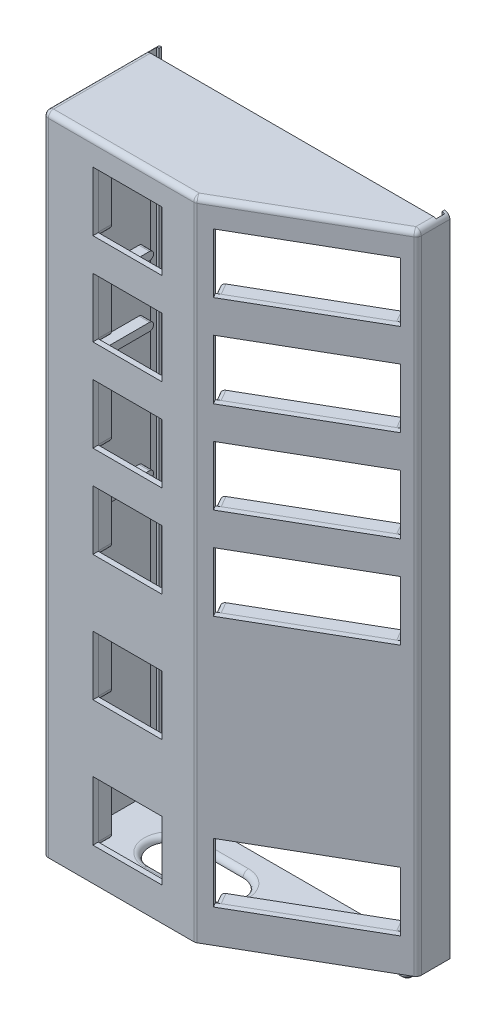
SolidWorks part; units mm, degrees
ref_plane "Front Plane" through (0, 0, 0) normal (0, 0, 1) x (1, 0, 0)
ref_plane "Top Plane" through (0, 0, 0) normal (0, 1, 0) x (1, 0, 0)
ref_plane "Right Plane" through (0, 0, 0) normal (1, 0, 0) x (0, 0, -1)
sketch "Sketch2" plane through (0, 0, 0) normal (0, 1, 0) x (1, 0, 0)
  line L0 (-55, -21.2241) -> (-55, 21.2241)
  line L1 (-55, 21.2241) -> (55, 21.2241)
  line L2 (55, 21.2241) -> (55, 9.3594)
  line L3 (55, 9.3594) -> (2.0277, -21.2241)
  line L4 (2.0277, -21.2241) -> (-55, -21.2241)
  line L5 (0, 21.2241) -> (0, -21.2241) construction
  point P11 (0, 21.2241)
  point P12 (0, 0)
  dimension "D1" = 42.4483
  dimension "D2" = 110
  dimension "D3" = 57.0277
  dimension "D4" = 30
extrude "Main Body" add sketch "Sketch2" along normal blind 241.93
shell "Shell1" thickness 2 removed face at (0, 120.965, -21.2241)
sketch "Sketch3" plane through (0, 0, 21.2241) normal (0, 0, 1) x (1, 0, 0)
  line L1 (-36.2923, 34.72) -> (-10.4223, 34.72)
  line L2 (-36.2923, 34.72) -> (-36.2923, 12.45)
  line L3 (-36.2923, 12.45) -> (-10.4223, 12.45)
  line L4 (-10.4223, 34.72) -> (-10.4223, 12.45)
  line L5 (-36.2923, 81.89) -> (-10.4223, 81.89)
  line L6 (-36.2923, 81.89) -> (-36.2923, 59.62)
  line L7 (-36.2923, 59.62) -> (-10.4223, 59.62)
  line L8 (-10.4223, 81.89) -> (-10.4223, 59.62)
  line L9 (-36.2923, 129.06) -> (-10.4223, 129.06)
  line L10 (-36.2923, 129.06) -> (-36.2923, 106.79)
  line L11 (-36.2923, 106.79) -> (-10.4223, 106.79)
  line L12 (-10.4223, 129.06) -> (-10.4223, 106.79)
  line L13 (-36.2923, 163.53) -> (-10.4223, 163.53)
  line L14 (-36.2923, 163.53) -> (-36.2923, 141.26)
  line L15 (-36.2923, 141.26) -> (-10.4223, 141.26)
  line L16 (-10.4223, 163.53) -> (-10.4223, 141.26)
  line L17 (-36.2923, 198) -> (-10.4223, 198)
  line L18 (-36.2923, 198) -> (-36.2923, 175.73)
  line L19 (-36.2923, 175.73) -> (-10.4223, 175.73)
  line L20 (-10.4223, 198) -> (-10.4223, 175.73)
  line L21 (-36.2923, 232.47) -> (-10.4223, 232.47)
  line L22 (-36.2923, 232.47) -> (-36.2923, 210.2)
  line L23 (-36.2923, 210.2) -> (-10.4223, 210.2)
  line L24 (-10.4223, 232.47) -> (-10.4223, 210.2)
  line L26 (-55, 0) -> (2.0277, 0) construction
  line L27 (-55, 241.93) -> (-55, 0) construction
  point P24 (-36.2923, 23.585)
  point P29 (-36.2923, 70.755)
  point P30 (-36.2923, 117.925)
  point P31 (-36.2923, 152.395)
  point P32 (-36.2923, 186.865)
  point P33 (-36.2923, 221.335)
  point P34 (-23.3573, 12.45)
  dimension "D1" = 22.27
  dimension "D2" = 25.87
  dimension "D3" = 23.585
  dimension "D4" = 47.17
  dimension "D5" = 47.17
  dimension "D6" = 34.47
  dimension "D7" = 34.47
  dimension "D8" = 34.47
  dimension "D9" = 31.6427
extrude "Single Cutouts" cut sketch "Sketch3" against normal through all both and the other way through all
sketch "Sketch4" plane through (9.6973, 0, 16.7961) normal (0.5, 0, 0.866) x (0.866, 0, -0.5)
  line L1 (-3.856, 232.47) -> (47.394, 232.47)
  line L2 (-3.856, 232.47) -> (-3.856, 210.2)
  line L3 (-3.856, 210.2) -> (47.394, 210.2)
  line L4 (47.394, 232.47) -> (47.394, 210.2)
  line L5 (-3.856, 198) -> (47.394, 198)
  line L6 (-3.856, 198) -> (-3.856, 175.73)
  line L7 (-3.856, 175.73) -> (47.394, 175.73)
  line L8 (47.394, 198) -> (47.394, 175.73)
  line L9 (-3.856, 163.53) -> (47.394, 163.53)
  line L10 (-3.856, 163.53) -> (-3.856, 141.26)
  line L11 (-3.856, 141.26) -> (47.394, 141.26)
  line L12 (47.394, 163.53) -> (47.394, 141.26)
  line L13 (-3.856, 129.06) -> (47.394, 129.06)
  line L14 (-3.856, 129.06) -> (-3.856, 106.79)
  line L15 (-3.856, 106.79) -> (47.394, 106.79)
  line L16 (47.394, 129.06) -> (47.394, 106.79)
  line L17 (-3.856, 34.72) -> (47.394, 34.72)
  line L18 (-3.856, 34.72) -> (-3.856, 12.45)
  line L19 (-3.856, 12.45) -> (47.394, 12.45)
  line L20 (47.394, 34.72) -> (47.394, 12.45)
  line L21 (-42.0421, 34.72) -> (-19.638, 34.72) construction
  line L22 (-42.0421, 129.06) -> (-19.638, 129.06) construction
  line L23 (-42.0421, 163.53) -> (-19.638, 163.53) construction
  line L24 (-42.0421, 198) -> (-19.638, 198) construction
  line L25 (-42.0421, 232.47) -> (-19.638, 232.47) construction
  line L26 (-19.638, 232.47) -> (-19.638, 210.2) construction
  line L27 (-8.856, 241.93) -> (-8.856, 0) construction
  dimension "D1" = 51.25
  dimension "D2" = 5
extrude "Double Cutouts" cut sketch "Sketch4" against normal through all both and the other way through all
sketch "Sketch5" plane through (0, 0, 0) normal (0, -1, 0) x (1, 0, 0)
  line L0 (-55, -21.2241) -> (-55, 21.2241) construction
  line L1 (-55, 21.2241) -> (2.0277, 21.2241) construction
  line L2 (55, -21.2241) -> (-55, -21.2241) construction
  line L3 (55, -9.3594) -> (55, -21.2241) construction
  circle A0 centre (47, -13.2241) radius 2.75
  circle A1 centre (-47, 13.2241) radius 2.75
  circle A2 centre (-47, -13.2241) radius 2.75
  circle A3 centre (-2, 13.2241) radius 2.75
  dimension "D3" = 8
  dimension "D4" = 5.5
  dimension "D5" = 45
  dimension "D6" = 8
  dimension "D1" = 8
  dimension "D2" = 8
extrude "Mating Studs" add sketch "Sketch5" along normal blind 5
chamfer "Mating Stud Chamfer" distance 1 angle 45 4 edges at (47, -5, -15.9741) (-47, -5, -15.9741) (-47, -5, 10.4741) (-2, -5, 10.4741)
sketch "Sketch6" plane through (0, 0, 0) normal (0, -1, 0) x (1, 0, 0)
  line L0 (-30, -1.2241) -> (-10, -1.2241) construction
  line L1 (-30, 6.2759) -> (-10, 6.2759)
  line L2 (-30, -8.7241) -> (-10, -8.7241)
  line L3 (55, -21.2241) -> (-55, -21.2241) construction
  line L4 (-55, -21.2241) -> (-55, 21.2241) construction
  arc A0 (-30, 6.2759) -> (-30, -8.7241) centre (-30, -1.2241) ccw
  arc A1 (-10, -8.7241) -> (-10, 6.2759) centre (-10, -1.2241) ccw
  point P2 (-20, -1.2241)
  dimension "D4" = 25
  dimension "D1" = 15
  dimension "D2" = 20
  dimension "D3" = 20
extrude "Pass Thru" cut sketch "Sketch6" against normal up to next
sketch "Sketch7" plane through (0, 0, 19.2241) normal (0, 0, -1) x (-1, 0, 0)
  line L0 (8.4073, 12.585) -> (8.4073, 34.585) construction
  line L1 (6.4073, 12.585) -> (6.4073, 34.585)
  line L2 (10.4073, 12.585) -> (10.4073, 34.585)
  line L3 (8.4073, 59.755) -> (8.4073, 81.755) construction
  line L4 (6.4073, 59.755) -> (6.4073, 81.755)
  line L5 (10.4073, 59.755) -> (10.4073, 81.755)
  line L6 (8.4073, 106.925) -> (8.4073, 128.925) construction
  line L7 (6.4073, 106.925) -> (6.4073, 128.925)
  line L8 (10.4073, 106.925) -> (10.4073, 128.925)
  line L9 (8.4073, 141.395) -> (8.4073, 163.395) construction
  line L10 (6.4073, 141.395) -> (6.4073, 163.395)
  line L11 (10.4073, 141.395) -> (10.4073, 163.395)
  line L12 (8.4073, 232.335) -> (8.4073, 210.335) construction
  line L13 (10.4073, 232.335) -> (10.4073, 210.335)
  line L14 (6.4073, 232.335) -> (6.4073, 210.335)
  line L15 (8.4073, 197.865) -> (8.4073, 175.865) construction
  line L16 (10.4073, 197.865) -> (10.4073, 175.865)
  line L17 (6.4073, 197.865) -> (6.4073, 175.865)
  line L18 (23.3573, 12.45) -> (23.3573, 81.89) construction
  line L19 (10.4223, 12.45) -> (36.2923, 12.45) construction
  line L20 (36.2923, 81.89) -> (10.4223, 81.89) construction
  line L21 (38.3073, 12.585) -> (38.3073, 34.585) construction
  line L22 (40.3073, 12.585) -> (40.3073, 34.585)
  line L23 (36.3073, 12.585) -> (36.3073, 34.585)
  line L24 (38.3073, 59.755) -> (38.3073, 81.755) construction
  line L25 (40.3073, 59.755) -> (40.3073, 81.755)
  line L26 (36.3073, 59.755) -> (36.3073, 81.755)
  line L27 (38.3073, 106.925) -> (38.3073, 128.925) construction
  line L28 (40.3073, 106.925) -> (40.3073, 128.925)
  line L29 (36.3073, 106.925) -> (36.3073, 128.925)
  line L30 (38.3073, 141.395) -> (38.3073, 163.395) construction
  line L31 (40.3073, 141.395) -> (40.3073, 163.395)
  line L32 (36.3073, 141.395) -> (36.3073, 163.395)
  line L33 (38.3073, 232.335) -> (38.3073, 210.335) construction
  line L34 (36.3073, 232.335) -> (36.3073, 210.335)
  line L35 (40.3073, 232.335) -> (40.3073, 210.335)
  line L36 (38.3073, 197.865) -> (38.3073, 175.865) construction
  line L37 (36.3073, 197.865) -> (36.3073, 175.865)
  line L38 (40.3073, 197.865) -> (40.3073, 175.865)
  line L39 (10.4223, 34.72) -> (10.4223, 12.45) construction
  line L40 (-5.3579, 23.585) -> (8.4073, 23.585) construction
  line L41 (-5.3579, 12.45) -> (-5.3579, 34.72) construction
  line L42 (-5.3579, 221.335) -> (8.4073, 221.335) construction
  line L43 (-5.3579, 210.2) -> (-5.3579, 232.47) construction
  line L44 (8.4073, 186.865) -> (-5.3579, 186.865) construction
  line L45 (-5.3579, 175.73) -> (-5.3579, 198) construction
  line L46 (-5.3579, 152.395) -> (8.4073, 152.395) construction
  line L47 (-5.3579, 141.26) -> (-5.3579, 163.53) construction
  line L48 (-5.3579, 117.925) -> (8.4073, 117.925) construction
  line L49 (-5.3579, 106.79) -> (-5.3579, 129.06) construction
  line L50 (10.4223, 70.755) -> (8.4073, 70.755) construction
  line L51 (10.4223, 81.89) -> (10.4223, 59.62) construction
  arc A0 (6.4073, 12.585) -> (10.4073, 12.585) centre (8.4073, 12.585) ccw
  arc A1 (10.4073, 34.585) -> (6.4073, 34.585) centre (8.4073, 34.585) ccw
  arc A2 (6.4073, 59.755) -> (10.4073, 59.755) centre (8.4073, 59.755) ccw
  arc A3 (10.4073, 81.755) -> (6.4073, 81.755) centre (8.4073, 81.755) ccw
  arc A4 (6.4073, 106.925) -> (10.4073, 106.925) centre (8.4073, 106.925) ccw
  arc A5 (10.4073, 128.925) -> (6.4073, 128.925) centre (8.4073, 128.925) ccw
  arc A6 (6.4073, 141.395) -> (10.4073, 141.395) centre (8.4073, 141.395) ccw
  arc A7 (10.4073, 163.395) -> (6.4073, 163.395) centre (8.4073, 163.395) ccw
  arc A8 (10.4073, 232.335) -> (6.4073, 232.335) centre (8.4073, 232.335) ccw
  arc A9 (6.4073, 210.335) -> (10.4073, 210.335) centre (8.4073, 210.335) ccw
  arc A10 (10.4073, 197.865) -> (6.4073, 197.865) centre (8.4073, 197.865) ccw
  arc A11 (6.4073, 175.865) -> (10.4073, 175.865) centre (8.4073, 175.865) ccw
  arc A12 (40.3073, 12.585) -> (36.3073, 12.585) centre (38.3073, 12.585) cw
  arc A13 (36.3073, 34.585) -> (40.3073, 34.585) centre (38.3073, 34.585) cw
  arc A14 (40.3073, 59.755) -> (36.3073, 59.755) centre (38.3073, 59.755) cw
  arc A15 (36.3073, 81.755) -> (40.3073, 81.755) centre (38.3073, 81.755) cw
  arc A16 (40.3073, 106.925) -> (36.3073, 106.925) centre (38.3073, 106.925) cw
  arc A17 (36.3073, 128.925) -> (40.3073, 128.925) centre (38.3073, 128.925) cw
  arc A18 (40.3073, 141.395) -> (36.3073, 141.395) centre (38.3073, 141.395) cw
  arc A19 (36.3073, 163.395) -> (40.3073, 163.395) centre (38.3073, 163.395) cw
  arc A20 (36.3073, 232.335) -> (40.3073, 232.335) centre (38.3073, 232.335) cw
  arc A21 (40.3073, 210.335) -> (36.3073, 210.335) centre (38.3073, 210.335) cw
  arc A22 (36.3073, 197.865) -> (40.3073, 197.865) centre (38.3073, 197.865) cw
  arc A23 (40.3073, 175.865) -> (36.3073, 175.865) centre (38.3073, 175.865) cw
  point P4 (8.4073, 23.585)
  point P9 (8.4073, 70.755)
  point P21 (8.4073, 117.925)
  point P28 (8.4073, 152.395)
  point P37 (8.4073, 221.335)
  point P46 (8.4073, 186.865)
  point P64 (38.3073, 23.585)
  point P71 (38.3073, 70.755)
  point P78 (38.3073, 117.925)
  point P85 (38.3073, 152.395)
  point P92 (38.3073, 221.335)
  point P99 (38.3073, 186.865)
  dimension "D1" = 0.015
  dimension "D2" = 4
  dimension "D3" = 22
extrude "PCB Mounts  - Single" add sketch "Sketch7" along normal blind 5
sketch "Sketch9" plane through (8.6973, 0, 15.0641) normal (-0.5, 0, -0.866) x (-0.866, 0, 0.5)
  line L0 (-45.844, 234.07) -> (2.306, 234.07) construction
  line L1 (-45.844, 235.57) -> (2.306, 235.57)
  line L2 (-45.844, 232.57) -> (2.306, 232.57)
  line L3 (-45.844, 208.6) -> (2.306, 208.6) construction
  line L4 (-45.844, 210.1) -> (2.306, 210.1)
  line L5 (-45.844, 207.1) -> (2.306, 207.1)
  line L6 (-45.844, 199.6) -> (2.306, 199.6) construction
  line L9 (-45.844, 201.1) -> (2.306, 201.1)
  line L10 (-45.844, 198.1) -> (2.306, 198.1)
  line L11 (-45.844, 174.13) -> (2.306, 174.13) construction
  line L12 (-45.844, 175.63) -> (2.306, 175.63)
  line L13 (-45.844, 172.63) -> (2.306, 172.63)
  line L14 (-45.844, 165.13) -> (2.306, 165.13) construction
  line L15 (-45.844, 166.63) -> (2.306, 166.63)
  line L16 (-45.844, 163.63) -> (2.306, 163.63)
  line L17 (-45.844, 139.66) -> (2.306, 139.66) construction
  line L18 (-45.844, 141.16) -> (2.306, 141.16)
  line L19 (-45.844, 138.16) -> (2.306, 138.16)
  line L20 (-45.844, 130.66) -> (2.306, 130.66) construction
  line L21 (-45.844, 132.16) -> (2.306, 132.16)
  line L22 (-45.844, 129.16) -> (2.306, 129.16)
  line L23 (-45.844, 105.19) -> (2.306, 105.19) construction
  line L24 (-45.844, 106.69) -> (2.306, 106.69)
  line L25 (-45.844, 103.69) -> (2.306, 103.69)
  line L26 (-45.844, 36.32) -> (2.306, 36.32) construction
  line L27 (-45.844, 37.82) -> (2.306, 37.82)
  line L28 (-45.844, 34.82) -> (2.306, 34.82)
  line L29 (-45.844, 10.85) -> (2.306, 10.85) construction
  line L30 (-45.844, 12.35) -> (2.306, 12.35)
  line L31 (-45.844, 9.35) -> (2.306, 9.35)
  line L32 (3.856, 34.72) -> (-47.394, 34.72) construction
  line L33 (-21.769, 10.85) -> (-21.769, 12.45) construction
  line L34 (-47.394, 12.45) -> (3.856, 12.45) construction
  line L35 (-21.769, 12.45) -> (-21.769, 242.0592) construction
  line L36 (-47.394, 106.79) -> (3.856, 106.79) construction
  line L37 (3.856, 129.06) -> (-47.394, 129.06) construction
  line L38 (-47.394, 141.26) -> (3.856, 141.26) construction
  line L39 (3.856, 163.53) -> (-47.394, 163.53) construction
  line L40 (-47.394, 175.73) -> (3.856, 175.73) construction
  line L41 (3.856, 198) -> (-47.394, 198) construction
  line L42 (-47.394, 210.2) -> (3.856, 210.2) construction
  line L43 (3.856, 232.47) -> (-47.394, 232.47) construction
  arc A0 (-45.844, 235.57) -> (-45.844, 232.57) centre (-45.844, 234.07) ccw
  arc A1 (2.306, 232.57) -> (2.306, 235.57) centre (2.306, 234.07) ccw
  arc A2 (-45.844, 210.1) -> (-45.844, 207.1) centre (-45.844, 208.6) ccw
  arc A3 (2.306, 207.1) -> (2.306, 210.1) centre (2.306, 208.6) ccw
  arc A6 (-45.844, 201.1) -> (-45.844, 198.1) centre (-45.844, 199.6) ccw
  arc A7 (2.306, 198.1) -> (2.306, 201.1) centre (2.306, 199.6) ccw
  arc A8 (-45.844, 175.63) -> (-45.844, 172.63) centre (-45.844, 174.13) ccw
  arc A9 (2.306, 172.63) -> (2.306, 175.63) centre (2.306, 174.13) ccw
  arc A10 (-45.844, 166.63) -> (-45.844, 163.63) centre (-45.844, 165.13) ccw
  arc A11 (2.306, 163.63) -> (2.306, 166.63) centre (2.306, 165.13) ccw
  arc A12 (-45.844, 141.16) -> (-45.844, 138.16) centre (-45.844, 139.66) ccw
  arc A13 (2.306, 138.16) -> (2.306, 141.16) centre (2.306, 139.66) ccw
  arc A14 (-45.844, 132.16) -> (-45.844, 129.16) centre (-45.844, 130.66) ccw
  arc A15 (2.306, 129.16) -> (2.306, 132.16) centre (2.306, 130.66) ccw
  arc A16 (-45.844, 106.69) -> (-45.844, 103.69) centre (-45.844, 105.19) ccw
  arc A17 (2.306, 103.69) -> (2.306, 106.69) centre (2.306, 105.19) ccw
  arc A18 (-45.844, 37.82) -> (-45.844, 34.82) centre (-45.844, 36.32) ccw
  arc A19 (2.306, 34.82) -> (2.306, 37.82) centre (2.306, 36.32) ccw
  arc A20 (-45.844, 12.35) -> (-45.844, 9.35) centre (-45.844, 10.85) ccw
  arc A21 (2.306, 9.35) -> (2.306, 12.35) centre (2.306, 10.85) ccw
  point P4 (-21.769, 234.07)
  point P9 (-21.769, 208.6)
  point P20 (-21.769, 199.6)
  point P21 (0, 0)
  point P26 (-21.769, 174.13)
  point P37 (-21.769, 165.13)
  point P46 (-21.769, 139.66)
  point P55 (-21.769, 130.66)
  point P64 (-21.769, 105.19)
  point P73 (-21.769, 36.32)
  point P82 (-21.769, 10.85)
  point P94 (0, 0)
  point P95 (0, 0)
  point P96 (0, 0)
  point P97 (0, 0)
  point P98 (0, 0)
  point P99 (0, 0)
  point P100 (0, 0)
  point P101 (0, 0)
  point P102 (0, 0)
  dimension "D1" = 3
  dimension "D2" = 48.15
  dimension "D3" = 0.1
  dimension "D4" = 0.1
  dimension "D5" = 0.1
  dimension "D6" = 0.1
  dimension "D7" = 0.1
  dimension "D8" = 0.1
  dimension "D9" = 0.1
  dimension "D10" = 0.1
  dimension "D11" = 0.1
  dimension "D12" = 0.1
extrude "PCB Mounts - Double" add sketch "Sketch9" along normal blind 5
sketch "Sketch11" plane through (-53, 0, 0) normal (1, 0, 0) x (0, 0, -1)
  line L0 (-12.2759, 228.43) -> (12.7241, 228.43) construction
  line L1 (-12.2759, 229.93) -> (12.7241, 229.93)
  line L2 (-12.2759, 226.93) -> (12.7241, 226.93)
  line L3 (-12.2759, 180.28) -> (12.7241, 180.28) construction
  line L4 (-12.2759, 181.78) -> (12.7241, 181.78)
  line L5 (-12.2759, 178.78) -> (12.7241, 178.78)
  line L6 (-12.2759, 157.28) -> (12.7241, 157.28) construction
  line L7 (-12.2759, 158.78) -> (12.7241, 158.78)
  line L8 (-12.2759, 155.78) -> (12.7241, 155.78)
  line L9 (-12.2759, 109.13) -> (12.7241, 109.13) construction
  line L10 (-12.2759, 110.63) -> (12.7241, 110.63)
  line L11 (-12.2759, 107.63) -> (12.7241, 107.63)
  line L12 (-12.2759, 71.13) -> (12.7241, 71.13) construction
  line L13 (-12.2759, 72.63) -> (12.7241, 72.63)
  line L14 (-12.2759, 69.63) -> (12.7241, 69.63)
  line L15 (-12.2759, 22.98) -> (12.7241, 22.98) construction
  line L16 (-12.2759, 24.48) -> (12.7241, 24.48)
  line L17 (-12.2759, 21.48) -> (12.7241, 21.48)
  line L18 (21.2241, 2) -> (-19.2241, 2) construction
  line L19 (21.2241, 239.93) -> (21.2241, 2) construction
  line L20 (0.2241, 22.98) -> (0.2241, 71.13) construction
  line L21 (0.2241, 71.13) -> (0.2241, 109.13) construction
  line L22 (0.2241, 109.13) -> (0.2241, 157.28) construction
  line L23 (0.2241, 157.28) -> (0.2241, 180.28) construction
  line L24 (0.2241, 180.28) -> (0.2241, 228.43) construction
  arc A0 (-12.2759, 229.93) -> (-12.2759, 226.93) centre (-12.2759, 228.43) ccw
  arc A1 (12.7241, 226.93) -> (12.7241, 229.93) centre (12.7241, 228.43) ccw
  arc A2 (-12.2759, 181.78) -> (-12.2759, 178.78) centre (-12.2759, 180.28) ccw
  arc A3 (12.7241, 178.78) -> (12.7241, 181.78) centre (12.7241, 180.28) ccw
  arc A4 (-12.2759, 158.78) -> (-12.2759, 155.78) centre (-12.2759, 157.28) ccw
  arc A5 (12.7241, 155.78) -> (12.7241, 158.78) centre (12.7241, 157.28) ccw
  arc A6 (-12.2759, 110.63) -> (-12.2759, 107.63) centre (-12.2759, 109.13) ccw
  arc A7 (12.7241, 107.63) -> (12.7241, 110.63) centre (12.7241, 109.13) ccw
  arc A8 (-12.2759, 72.63) -> (-12.2759, 69.63) centre (-12.2759, 71.13) ccw
  arc A9 (12.7241, 69.63) -> (12.7241, 72.63) centre (12.7241, 71.13) ccw
  arc A10 (-12.2759, 24.48) -> (-12.2759, 21.48) centre (-12.2759, 22.98) ccw
  arc A11 (12.7241, 21.48) -> (12.7241, 24.48) centre (12.7241, 22.98) ccw
  point P4 (0.2241, 228.43)
  point P9 (0.2241, 180.28)
  point P18 (0.2241, 157.28)
  point P27 (0.2241, 109.13)
  point P36 (0.2241, 71.13)
  point P45 (0.2241, 22.98)
  dimension "D1" = 20.98
  dimension "D2" = 3
  dimension "D3" = 25
  dimension "D4" = 21
  dimension "D5" = 48.15
  dimension "D6" = 38
  dimension "D7" = 48.15
  dimension "D8" = 23
  dimension "D9" = 48.15
extrude "PCB Mounts - Sides" add sketch "Sketch11" along normal blind 4
fillet "Fillet1" radius 2 7 edges at (-55, 120.965, 21.2241) (2.0277, 120.965, 21.2241) (55, 120.965, -9.3594) (-55, 241.93, 0) (55, 241.93, -15.2918) (28.5139, 241.93, 5.9324) (-26.4861, 241.93, 21.2241)
sketch "Sketch13" plane through (0, 241.93, 0) normal (0, 1, 0) x (1, 0, 0)
  line L0 (-55, -19.2241) -> (-55, 21.2241) construction
  line L1 (-54, 20.2241) -> (-53, 20.2241)
  line L2 (-54, 20.2241) -> (-54, 17.0491)
  line L3 (-54, 17.0491) -> (54, 17.0491)
  line L4 (54, 20.2241) -> (54, 17.0491)
  line L5 (-53, 20.2241) -> (-53, 21.2241)
  line L6 (-53, 21.2241) -> (53, 21.2241)
  line L7 (53, 21.2241) -> (53, 20.2241)
  line L8 (53, 10.5141) -> (53, 21.2241) construction
  line L9 (-53, 21.2241) -> (-53, -19.2241) construction
  line L10 (53, 20.2241) -> (54, 20.2241)
  dimension "D1" = 3.175
  dimension "D2" = 1
  dimension "D3" = 1
  dimension "D4" = 1
extrude "Back Panel Cut" cut sketch "Sketch13" against normal through all both and the other way through all
fillet "Fillet2" radius 2 4 edges at (-20, 2, 6.2759) (-37.5, 2, -1.2241) (-20, 2, -8.7241) (-2.5, 2, -1.2241)
